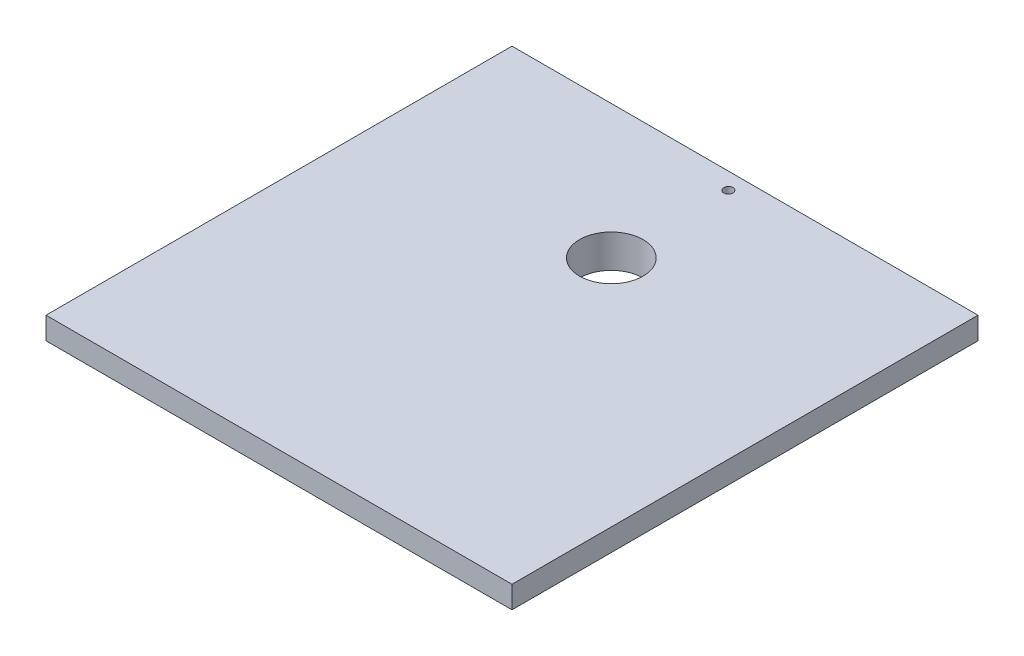
SolidWorks part; units mm, degrees
ref_plane "Front Plane" through (0, 0, 0) normal (0, 0, 1) x (1, 0, 0)
ref_plane "Top Plane" through (0, 0, 0) normal (0, 1, 0) x (1, 0, 0)
ref_plane "Right Plane" through (0, 0, 0) normal (1, 0, 0) x (0, 0, -1)
sketch "Sketch2" plane through (0, 0, 0) normal (0, 1, 0) x (1, 0, 0)
  line L1 (-105, -105) -> (105, -105)
  line L2 (-105, -105) -> (-105, 105)
  line L3 (-105, 105) -> (105, 105)
  line L4 (105, -105) -> (105, 105)
  line L5 (-105, -105) -> (105, 105) construction
  line L6 (-105, 105) -> (105, -105) construction
  point P0 (0, 0)
  dimension "D1" = 210
  dimension "D2" = 210
extrude "Boss-Extrude1" add sketch "Sketch2" along normal blind 10
sketch "Sketch3" plane through (0, 0, 0) normal (0, -1, 0) x (1, 0, 0)
  line L1 (-89.925, -89.925) -> (89.925, -89.925)
  line L2 (-89.925, -89.925) -> (-89.925, 89.925)
  line L3 (-89.925, 89.925) -> (89.925, 89.925)
  line L4 (89.925, -89.925) -> (89.925, 89.925)
  line L5 (-89.925, -89.925) -> (89.925, 89.925) construction
  line L6 (-89.925, 89.925) -> (89.925, -89.925) construction
  point P0 (0, 0)
  dimension "D1" = 179.85
  dimension "D2" = 179.85
extrude "Boss-Extrude2" add sketch "Sketch3" along normal blind 5 draft 2
sketch "Sketch4" plane through (0, 10, 0) normal (0, 1, 0) x (1, 0, 0)
  line L0 (-89.7504, 89.7504) -> (89.7504, 89.7504) construction
  circle A0 centre (0, 44.7504) radius 14.3
  dimension "D1" = 28.6
  dimension "D2" = 45
extrude "Cut-Extrude1" cut sketch "Sketch4" against normal up to surface (15 mm away) up to face at (0, -5, 0)
sketch "Sketch6" plane through (0, 10, 0) normal (0, 1, 0) x (1, 0, 0)
  line L0 (105, 105) -> (-105, 105) construction
  circle A0 centre (0, 97.5) radius 2.1
  circle A1 centre (0, 97.5) radius 2.1
  circle A2 centre (0, 97.5) radius 2.1
  circle A3 centre (0, 97.5) radius 2.1
  dimension "D1" = 4.2
  dimension "D2" = 7.5
  dimension "D3" = 4
extrude "Cut-Extrude2" cut sketch "Sketch6" against normal up to surface (10 mm away) contours A2 | A3 | A0 | A1 region at (0, 10, -97.5) up to face at (0, 0, 0)
fillet "Fillet1" radius 5 4 edges at (89.8377, -2.5, 89.8377) (89.8377, -2.5, -89.8377) (-89.8377, -2.5, -89.8377) (-89.8377, -2.5, 89.8377)
